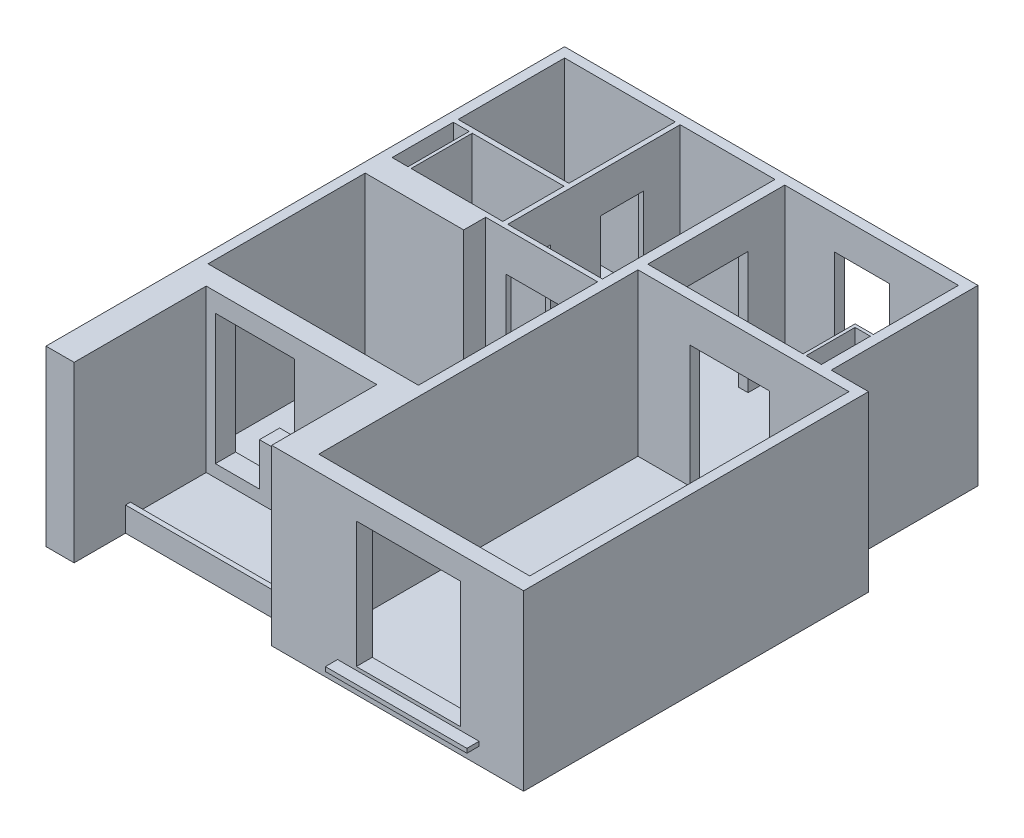
SolidWorks part; units mm, degrees
ref_plane "Спереди" through (0, 0, 0) normal (0, 0, 1) x (1, 0, 0)
ref_plane "Сверху" through (0, 0, 0) normal (0, 1, 0) x (1, 0, 0)
ref_plane "Справа" through (0, 0, 0) normal (1, 0, 0) x (0, 0, -1)
other "Configuration Table"
sketch "чертеж" plane through (0, 0, 0) normal (0, 1, 0) x (1, 0, 0)
  line L0 (-122.4645, -5934.5928) -> (200.8688, -5934.5928) construction
  line L1 (11.3792, -6202.3586) -> (334.7125, -6202.3586) construction
  line L2 (-29.7674, 42.6262) -> (294.8993, 42.6262) construction
  line L3 (-41.8231, 39.2884) -> (282.8435, 39.2884) construction
  line L4 (2418.4622, -1094.6493) -> (2743.1288, -1094.6493) construction
  line L5 (-60.4594, 42.9789) -> (264.2073, 42.9789) construction
  line L6 (-48.7728, 66.0913) -> (275.8939, 66.0913) construction
  line L7 (-42.5542, 93.9023) -> (282.1124, 93.9023) construction
  line L8 (134.2311, 87.3942) -> (458.8978, 87.3942) construction
  line L9 (-47.3906, 51.9395) -> (277.2761, 51.9395) construction
  line L10 (-66.0858, -48.647) -> (431.2475, -48.647) construction
sketch "Эскиз по чертежу" plane through (0, 0, 0) normal (0, 1, 0) x (1, 0, 0)
  line L0 (0, 0) -> (0, 8400) construction
  line L1 (0, 8400) -> (1925, 8400) construction
  line L2 (6600, 8400) -> (6600, 6000) construction
  line L4 (7200, 6000) -> (7200, 600) construction
  line L5 (7200, 600) -> (3600, 600) construction
  line L6 (3600, 600) -> (3600, 8400) construction
  line L7 (3600, 2400) -> (0, 2400) construction
  line L8 (3600, 5475) -> (0, 5475) construction
  line L32 (6600, 6000) -> (7200, 6000) construction
  line L33 (0, 870) -> (3600, 870) construction
  line L37 (0, 1050) -> (3600, 1050) construction
  line L40 (1925, 5475) -> (1925, 6550) construction
  line L42 (1925, 6550) -> (1925, 8400) construction
  line L45 (1925, 8400) -> (3600, 8400) construction
  line L46 (3600, 8400) -> (6600, 8400) construction
  line L49 (1925, 6550) -> (0, 6550) construction
  dimension "D1" = 600
  dimension "D2" = 1800
  dimension "D3" = 3600
  dimension "D4" = 1530
  dimension "D5" = 600
  dimension "D6" = 3600
  dimension "D7" = 3600
  dimension "D8" = 2400
  dimension "D9" = 2925
  dimension "D10" = 1925
  dimension "D11" = 1850
  dimension "D12" = 1350
sketch "Эскиз3" plane through (0, 0, 0) normal (0, 1, 0) x (1, 0, 0)
  line L1 (3520, 6130) -> (3680, 6130)
  line L2 (4555, 700) -> (4555, 1200) construction
  line L11 (80, 8320) -> (3520, 8320)
  line L15 (3520, 8320) -> (3520, 7720)
  line L16 (3520, 7720) -> (3680, 7720)
  line L17 (3680, 7720) -> (3680, 8320)
  line L20 (6520, 6080) -> (5830, 6080)
  line L21 (-80, 8480) -> (4495, 8480)
  line L22 (6520, 8320) -> (6520, 6080)
  line L24 (4495, 8480) -> (4495, 8320)
  line L25 (4495, 8320) -> (3680, 8320)
  line L26 (6680, 8480) -> (5395, 8480)
  line L29 (7130, 5920) -> (7130, 700)
  line L30 (4555, 700) -> (3680, 700)
  line L32 (6255, 540) -> (7290, 540)
  line L33 (7290, 540) -> (7290, 6080)
  line L34 (7290, 6080) -> (6680, 6080)
  line L35 (6680, 6080) -> (6680, 8480)
  line L39 (5395, 8480) -> (5395, 8320)
  line L40 (5395, 8320) -> (6520, 8320)
  line L41 (5830, 6080) -> (5830, 5920)
  line L42 (5830, 5920) -> (7130, 5920)
  line L45 (-80, 8480) -> (-80, 0)
  line L46 (-80, 0) -> (80, 0)
  line L47 (3680, 6080) -> (4530, 6080)
  line L52 (80, 0) -> (80, 8320)
  line L60 (3680, 700) -> (3680, 5920)
  line L68 (3520, 6130) -> (3520, 540)
  line L69 (4530, 6080) -> (4530, 5920)
  line L70 (4530, 5920) -> (3680, 5920)
  line L71 (7130, 700) -> (6255, 700)
  line L72 (6255, 540) -> (6255, 700)
  line L73 (3520, 540) -> (4555, 540)
  line L74 (4555, 540) -> (4555, 700)
  line L76 (4555, 1200) -> (3680, 1200) construction
  line L77 (6255, 700) -> (6255, 1200) construction
  line L78 (4555, 1200) -> (6255, 1200) construction
  line L79 (6255, 1200) -> (7130, 1200) construction
  line L80 (3680, 6130) -> (3680, 6080)
  line L81 (3600, 8400) -> (6600, 8400) construction
  line L83 (0, 0) -> (0, 8400) construction
  dimension "D1" = 3440
  dimension "D2" = 3450
  dimension "D3" = 5220
  dimension "D4" = 1300
  dimension "D5" = 160
  dimension "D6" = 2840
  dimension "D7" = 160
  dimension "D8" = 160
  dimension "D9" = 2240
  dimension "D10" = 160
  dimension "D11" = 80
  dimension "D12" = 160
  dimension "D13" = 160
  dimension "D14" = 80
  dimension "D15" = 900
  dimension "D16" = 160
  dimension "D17" = 1125
  dimension "D18" = 600
  dimension "D19" = 160
  dimension "D20" = 850
  dimension "D21" = 1700
  dimension "D22" = 500
  dimension "D23" = 50
  dimension "D24" = 875
extrude "несущие стены" add sketch "Эскиз3" along normal blind 2640 separate body
sketch "Эскиз8" plane through (0, 0, 0) normal (0, 1, 0) x (1, 0, 0)
  line L0 (80, 8320) -> (3520, 8320) construction
  line L1 (80, 5500) -> (1690, 5500)
  line L2 (80, 5500) -> (80, 5060)
  line L3 (80, 5060) -> (1690, 5060)
  line L4 (1690, 5500) -> (1690, 5060)
  line L10 (80, 0) -> (80, 8320) construction
  dimension "D1" = 440
  dimension "D2" = 2820
  dimension "D5" = 1610
extrude "вытяжка кухня" add sketch "Эскиз8" along normal up to surface (2640 mm away) up to face at (6442.8571, 2640, -5160)
sketch "Эскиз5" plane through (0, 0, 0) normal (0, 1, 0) x (1, 0, 0)
  line L0 (80, 6580) -> (1890, 6580)
  line L1 (1970, 6200) -> (1970, 5500) construction
  line L2 (1890, 6580) -> (1890, 7020)
  line L3 (1890, 7020) -> (1970, 7020)
  line L4 (1970, 7020) -> (1970, 6200)
  line L5 (1970, 6200) -> (1890, 6200)
  line L6 (1890, 6200) -> (1890, 6500)
  line L7 (1890, 6500) -> (80, 6500)
  line L9 (80, 6500) -> (80, 6580)
  line L10 (1690, 5420) -> (2020, 5420)
  line L12 (2020, 5420) -> (2020, 5500)
  line L17 (2020, 5500) -> (1690, 5500)
  line L18 (1690, 5500) -> (1690, 5420)
  line L19 (3520, 5420) -> (2920, 5420)
  line L20 (3520, 6130) -> (3520, 540) construction
  line L21 (2920, 5420) -> (2920, 5500)
  line L22 (2920, 5500) -> (3520, 5500)
  line L23 (80, 0) -> (80, 5060) construction
  line L24 (3520, 5500) -> (3520, 5420)
  line L25 (1890, 8320) -> (1890, 7720)
  line L27 (1890, 7720) -> (1970, 7720)
  line L28 (1970, 7720) -> (1970, 8320)
  line L30 (1970, 8320) -> (1890, 8320)
  line L31 (80, 8320) -> (3520, 8320) construction
  line L32 (3520, 8320) -> (3520, 7720) construction
  dimension "D1" = 600
  dimension "D2" = 1810
  dimension "D3" = 1550
  dimension "D4" = 1740
  dimension "D5" = 80
  dimension "D6" = 700
  dimension "D7" = 700
  dimension "D8" = 1000
  dimension "D9" = 900
  dimension "D10" = 50
  dimension "D11" = 80
  dimension "D12" = 80
extrude "перегородки санузла" add sketch "Эскиз5" along normal up to surface (2640 mm away) up to face at (1923.5714, 2640, -6200)
sketch "Эскиз7" plane through (0, 0, 0) normal (0, 1, 0) x (1, 0, 0)
  line L0 (80, 0) -> (80, 5060) construction
  line L1 (530, 2490) -> (80, 2490)
  line L2 (380, 2160) -> (380, 0)
  line L3 (3170, 2160) -> (3170, 440)
  line L4 (3170, 440) -> (4555, 440)
  line L5 (380, 0) -> (80, 0)
  line L6 (80, 2490) -> (80, 0)
  line L7 (2920, 5420) -> (3520, 5420) construction
  line L8 (3170, 2160) -> (1820, 2160)
  line L9 (3520, 540) -> (4555, 540) construction
  line L10 (1820, 2490) -> (3520, 2490)
  line L14 (80, 5060) -> (1690, 5060) construction
  line L19 (4555, 540) -> (4555, 440)
  line L20 (6255, 540) -> (7290, 540)
  line L21 (6255, 540) -> (6255, 440)
  line L22 (6255, 440) -> (7290, 440)
  line L23 (7290, 540) -> (7290, 440)
  line L24 (1820, 2160) -> (1820, 2490)
  line L25 (3520, 2490) -> (3520, 540)
  line L26 (3520, 540) -> (4555, 540)
  line L27 (3520, 5420) -> (3520, 540) construction
  line L28 (6255, 540) -> (7290, 540) construction
  line L29 (380, 2160) -> (530, 2160)
  line L30 (530, 2160) -> (530, 2490)
  line L31 (4555, 540) -> (4555, 700) construction
  line L32 (6255, 700) -> (6255, 540) construction
  dimension "D1" = 2790
  dimension "D2" = 100
  dimension "D3" = 330
  dimension "D4" = 1290
  dimension "D5" = 150
  dimension "D6" = 450
  dimension "D7" = 2930
  dimension "D8" = 2570
extrude "лоджия" add sketch "Эскиз7" along normal up to surface (2640 mm away) up to face at (1798.2143, 2640, -6511.4286)
sketch "Эскиз9" plane through (0, 0, 0) normal (0, 1, 0) x (1, 0, 0)
  line L0 (340, 6500) -> (390, 6500)
  line L1 (6520, 6930) -> (6220, 6930)
  line L4 (6220, 6930) -> (6220, 6080)
  line L5 (80, 6500) -> (1890, 6500) construction
  line L6 (6520, 6080) -> (5830, 6080) construction
  line L7 (6270, 6880) -> (6520, 6880)
  line L8 (6270, 6880) -> (6270, 6080)
  line L11 (6520, 8320) -> (6520, 6080) construction
  line L13 (390, 5500) -> (340, 5500)
  line L14 (390, 6500) -> (390, 5500)
  line L15 (2020, 5500) -> (80, 5500) construction
  line L19 (340, 6500) -> (340, 5500)
  line L22 (1890, 6500) -> (1890, 6200) construction
  line L24 (6520, 6930) -> (6520, 6880)
  line L25 (6220, 6080) -> (6270, 6080)
  point P13 (6370, 6930)
  dimension "D1" = 850
  dimension "D2" = 50
  dimension "D4" = 300
  dimension "D8" = 50
  dimension "D11" = 1500
extrude "зсс" add sketch "Эскиз9" along normal up to surface (2640 mm away) up to face at (6442.8571, 2640, -5145.7143)
sketch "Эскиз11" plane through (0, 0, 0) normal (0, 1, 0) x (1, 0, 0)
  line L1 (1820, 2490) -> (1250, 2490)
  line L2 (1820, 2490) -> (1820, 2160)
  line L3 (1820, 2160) -> (1250, 2160)
  line L4 (1250, 2490) -> (1250, 2160)
  line L5 (530, 2160) -> (530, 2490) construction
  dimension "D1" = 720
extrude "лоджияперегородка" add sketch "Эскиз11" along normal blind 900
sketch "Эскиз4" plane through (0, 0, 0) normal (0, 1, 0) x (1, 0, 0)
  line L8 (-80, 8480) -> (6680, 8480)
  line L9 (6680, 8480) -> (6680, 6080)
  line L10 (6680, 6080) -> (7290, 6080)
  line L11 (7290, 6080) -> (7290, 440)
  line L13 (3170, 440) -> (3170, 840)
  line L14 (3170, 840) -> (380, 840)
  line L17 (-80, 0) -> (-80, 8480)
  line L18 (6680, 6080) -> (6680, 8480) construction
  line L19 (6680, 8480) -> (5395, 8480) construction
  line L20 (380, 920) -> (3170, 920) construction
  line L21 (380, 0) -> (380, 2160) construction
  line L22 (3170, 2160) -> (3170, 440) construction
  line L24 (380, 840) -> (380, 0)
  line L25 (380, 0) -> (-80, 0)
  line L26 (3170, 440) -> (7290, 440)
  line L27 (1820, 2160) -> (3170, 2160) construction
  line L28 (380, 0) -> (380, 2160) construction
  line L29 (-80, 0) -> (380, 0) construction
  dimension "D1" = 80
  dimension "D2" = 1240
extrude "пол" add sketch "Эскиз4" against normal blind 200
sketch "Эскиз49" plane through (0, 0, 0) normal (0, 1, 0) x (1, 0, 0)
  line L0 (380, 0) -> (380, 2160) construction
  line L1 (3170, 840) -> (380, 840)
  line L2 (3170, 840) -> (3170, 920)
  line L3 (3170, 920) -> (380, 920)
  line L4 (380, 840) -> (380, 920)
  dimension "D1" = 80
extrude "лоджиябордюрподокно" add sketch "Эскиз49" along normal blind 200
sketch "Эскиз50" plane through (0, 0, -440) normal (0, 0, 1) x (1, 0, 0)
  line L0 (4555, 0) -> (6255, 0) construction
  line L1 (4247.5, 145) -> (6562.5, 145)
  line L2 (4247.5, 145) -> (4247.5, 75)
  line L3 (4247.5, 75) -> (6562.5, 75)
  line L4 (6562.5, 145) -> (6562.5, 75)
  line L5 (5405, 0) -> (5405, 75) construction
  point P4 (5405, 75)
  point P5 (5405, 0)
  dimension "D1" = 70
  dimension "D2" = 2315
  dimension "D3" = 75
sketch "Эскиз54" plane through (0, 0, 0) normal (0, 1, 0) x (1, 0, 0)
  line L1 (530, 2490) -> (1250, 2490)
  line L2 (530, 2490) -> (530, 2160)
  line L3 (530, 2160) -> (1250, 2160)
  line L4 (1250, 2490) -> (1250, 2160)
extrude "лоджиябордюрподдверь" add sketch "Эскиз54" along normal blind 200
sketch "Эскиз51" plane through (0, 0, 0) normal (0, 1, 0) x (1, 0, 0)
  line L0 (4555, 440) -> (4555, 700) construction
  line L1 (6255, 440) -> (4555, 440)
  line L2 (6255, 440) -> (6255, 700)
  line L3 (6255, 700) -> (4555, 700)
  line L4 (4555, 440) -> (4555, 700)
extrude "залбордярподконо" add sketch "Эскиз51" along normal blind 200
extrude "подоконникнаружний" add sketch "Эскиз50" along normal blind 200
sketch "Эскиз53" plane through (0, 2640, 0) normal (0, 1, 0) x (1, 0, 0)
  line L1 (1820, 2490) -> (530, 2490)
  line L2 (1820, 2490) -> (1820, 2160)
  line L3 (1820, 2160) -> (530, 2160)
  line L4 (530, 2490) -> (530, 2160)
extrude "лоджияверх" add sketch "Эскиз53" against normal blind 310
sketch "Эскиз52" plane through (0, 2640, 0) normal (0, 1, 0) x (1, 0, 0)
  line L1 (4555, 440) -> (6255, 440)
  line L2 (4555, 440) -> (4555, 700)
  line L3 (4555, 700) -> (6255, 700)
  line L4 (6255, 440) -> (6255, 700)
extrude "залокноверх" add sketch "Эскиз52" against normal blind 380
sketch "Эскиз55" plane through (0, 2640, 0) normal (0, 1, 0) x (1, 0, 0)
  line L1 (4495, 8480) -> (5395, 8480)
  line L2 (4495, 8480) -> (4495, 8320)
  line L3 (4495, 8320) -> (5395, 8320)
  line L4 (5395, 8480) -> (5395, 8320)
extrude "входнаядверьверх" add sketch "Эскиз55" against normal blind 540
sketch "Эскиз65" plane through (0, 2640, 0) normal (0, 1, 0) x (1, 0, 0)
  line L0 (2020, 5500) -> (390, 5500) construction
  line L1 (1890, 6200) -> (1970, 6200)
  line L2 (1890, 6200) -> (1890, 5500)
  line L3 (1890, 5500) -> (1970, 5500)
  line L4 (1970, 6200) -> (1970, 5500)
  line L6 (1890, 7720) -> (1970, 7720)
  line L7 (1890, 7720) -> (1890, 7020)
  line L8 (1890, 7020) -> (1970, 7020)
  line L9 (1970, 7720) -> (1970, 7020)
  line L10 (3520, 7720) -> (3680, 7720)
  line L11 (3520, 7720) -> (3520, 6130)
  line L12 (3520, 6130) -> (3680, 6130)
  line L13 (3680, 7720) -> (3680, 6130)
  line L14 (2020, 5500) -> (2920, 5500)
  line L15 (2020, 5500) -> (2020, 5420)
  line L16 (2020, 5420) -> (2920, 5420)
  line L17 (2920, 5500) -> (2920, 5420)
  line L18 (4530, 6080) -> (5830, 6080)
  line L19 (4530, 6080) -> (4530, 5920)
  line L20 (4530, 5920) -> (5830, 5920)
  line L21 (5830, 6080) -> (5830, 5920)
extrude "остальные" add sketch "Эскиз65" against normal offset from surface (640 mm away) 2000 up to face at (3271.25, 0, -6277.0833)
sketch "Эскиз что надо" [suppressed] plane through (0, 0, 0) normal (0, 1, 0) x (1, 0, 0)
  line L0 (5525, 8300) -> (5525, 6100) construction
  line L5 (2000, 6240) -> (2000, 7000) construction
  line L6 (1850, 7000) -> (2000, 7000)
  line L7 (1850, 7000) -> (1850, 6620)
  line L8 (1850, 6620) -> (2000, 6620)
  line L9 (2000, 7000) -> (2000, 6620)
  line L10 (1850, 6490) -> (1850, 6240) construction
  line L11 (1850, 7700) -> (2000, 7700)
  line L12 (1850, 7700) -> (1850, 7320)
  line L13 (1850, 7320) -> (2000, 7320)
  line L14 (2000, 7700) -> (2000, 7320)
  line L15 (1850, 5540) -> (2000, 5540)
  line L16 (1850, 5540) -> (1850, 5790)
  line L17 (1850, 5790) -> (2000, 5790)
  line L18 (2000, 5540) -> (2000, 5790)
  line L19 (1850, 6490) -> (2000, 6490)
  line L20 (1850, 6490) -> (1850, 6240)
  line L21 (1850, 6240) -> (2000, 6240)
  line L22 (2000, 6490) -> (2000, 6240)
  line L23 (1850, 7000) -> (1850, 6620) construction
  line L28 (3500, 7700) -> (3700, 7700) construction
  line L29 (3500, 7700) -> (3500, 7420) construction
  line L30 (3500, 7420) -> (3700, 7420) construction
  line L31 (3700, 7700) -> (3700, 7420) construction
  line L32 (4550, 5900) -> (4550, 6100) construction
  line L35 (5850, 5900) -> (5450, 5900)
  line L36 (5850, 5900) -> (5850, 6100)
  line L37 (5850, 6100) -> (5450, 6100)
  line L38 (5450, 5900) -> (5450, 6100)
  line L39 (5375, 8300) -> (6500, 8300) construction
  line L40 (2000, 7420) -> (3500, 7420) construction
  line L41 (5375, 8500) -> (5375, 8300) construction
  line L42 (2380, 5540) -> (400, 5540) construction
  line L43 (1284, 2540) -> (2160, 2540)
  line L44 (1284, 2540) -> (1284, 2190)
  line L46 (1284, 2190) -> (2160, 2190)
  line L47 (2000, 7320) -> (2000, 6620) construction
  line L48 (2160, 2540) -> (2160, 2190)
  point P32 (1925, 6490)
  dimension "D8" = 900
  dimension "D1" = 700
  dimension "D2" = 700
  dimension "D3" = 150
  dimension "D5" = 100
sketch "Эскиз13" [suppressed] plane through (0, 0, 0) normal (0, 1, 0) x (1, 0, 0)
  line L1 (1850, 6490) -> (2000, 6490)
  line L2 (1850, 6490) -> (1850, 6240)
  line L3 (1850, 6240) -> (2000, 6240)
  line L4 (2000, 6490) -> (2000, 6240)
  line L5 (1850, 7000) -> (2000, 7000)
  line L6 (1850, 7000) -> (1850, 6620)
  line L7 (1850, 6620) -> (2000, 6620)
  line L8 (2000, 7000) -> (2000, 6620)
  line L9 (1284, 2540) -> (2160, 2540) construction
  line L10 (1284, 2540) -> (1284, 2190) construction
  line L11 (1284, 2190) -> (2160, 2190) construction
  line L12 (2160, 2540) -> (2160, 2190) construction
extrude "санузел вырез" [suppressed] cut sketch "Эскиз13" along normal through all
sketch "Эскиз14" [suppressed] plane through (0, 0, 0) normal (0, 1, 0) x (1, 0, 0)
  line L1 (5850, 6100) -> (5450, 6100)
  line L2 (5850, 6100) -> (5850, 5900)
  line L3 (5850, 5900) -> (5450, 5900)
  line L4 (5450, 6100) -> (5450, 5900)
  line L5 (1850, 5540) -> (2000, 5540)
  line L6 (1850, 5540) -> (1850, 5790)
  line L7 (1850, 5790) -> (2000, 5790)
  line L8 (2000, 5540) -> (2000, 5790)
  line L9 (1850, 7700) -> (2000, 7700)
  line L10 (1850, 7700) -> (1850, 7320)
  line L11 (1850, 7320) -> (2000, 7320)
  line L12 (2000, 7700) -> (2000, 7320)
extrude "наращивание стен" [suppressed] add sketch "Эскиз14" along normal through all separate body
sketch "Эскиз15" [suppressed] plane through (0, 0, 0) normal (0, 1, 0) x (1, 0, 0)
  line L12 (3700, 7700) -> (3500, 7700) construction
  line L29 (3700, 7420) -> (3700, 7700)
  line L30 (3700, 7700) -> (3500, 7700)
  line L32 (3500, 7700) -> (3500, 7420)
  line L36 (3500, 7420) -> (3700, 7420)
  line L39 (3500, 7700) -> (3500, 7420) construction
  line L40 (3700, 7700) -> (3700, 7420) construction
  line L46 (3500, 7700) -> (3700, 7700) construction
  line L47 (2000, 7420) -> (2800, 7420) construction
  line L48 (2000, 7420) -> (2000, 7500) construction
  line L49 (2000, 7500) -> (2800, 7500) construction
  line L50 (2800, 7420) -> (2800, 7500) construction
  dimension "D1" = 80
  dimension "D2" = 700
extrude "наращивание стен 2" [suppressed] add sketch "Эскиз15" along normal through all separate body
sketch "Эскиз37" [suppressed] plane through (0, 0, 0) normal (0, 1, 0) x (1, 0, 0)
  line L0 (3700, 700) -> (7100, 700)
  line L1 (7100, 700) -> (7100, 5900)
  line L2 (7100, 5900) -> (5850, 5900)
  line L3 (5850, 5900) -> (5850, 6100)
  line L7 (5850, 6100) -> (4550, 6100)
  line L8 (4550, 6100) -> (4550, 5900)
  line L9 (4550, 5900) -> (3700, 5900)
  line L10 (3700, 5900) -> (3700, 700)
extrude "зал" [suppressed] add sketch "Эскиз37" along normal blind 50 separate body
sketch "Эскиз38" [suppressed] plane through (0, 0, 0) normal (0, 1, 0) x (1, 0, 0)
  line L0 (460, 950) -> (3160, 950)
  line L1 (3160, 950) -> (3160, 2190)
  line L2 (3160, 2190) -> (2160, 2190)
  line L3 (2160, 2190) -> (2160, 2540)
  line L4 (2160, 2540) -> (3500, 2540)
  line L5 (3500, 5410) -> (3500, 2540) construction
  line L6 (3500, 2540) -> (3500, 5410)
  line L7 (3500, 5410) -> (3280, 5410)
  line L8 (3280, 5410) -> (3280, 5540)
  line L9 (3280, 5540) -> (2380, 5540)
  line L10 (2380, 5540) -> (2380, 5410)
  line L11 (2380, 5410) -> (1710, 5410)
  line L12 (1710, 5410) -> (1710, 5060)
  line L13 (1710, 5060) -> (100, 5060)
  line L14 (100, 5060) -> (100, 2540)
  line L15 (100, 2540) -> (560, 2540)
  line L16 (560, 2540) -> (560, 2190)
  line L17 (560, 2190) -> (460, 2190)
  line L18 (460, 2190) -> (460, 950)
  line L19 (460, 0) -> (460, 2190) construction
  line L20 (460, 900) -> (3160, 900) construction
  line L21 (3500, 2540) -> (2160, 2540) construction
  line L22 (3500, 2540) -> (1284, 2540) construction
  dimension "D1" = 50
extrude "кухня лоджия" [suppressed] add sketch "Эскиз38" along normal blind 50 separate body
sketch "Эскиз40" [suppressed] plane through (0, 0, 0) normal (0, 1, 0) x (1, 0, 0)
  line L0 (6200, 6100) -> (6200, 6950)
  line L1 (6200, 6950) -> (6500, 6950)
  line L2 (6500, 6950) -> (6500, 8300)
  line L3 (6500, 8300) -> (3700, 8300)
  line L4 (3700, 8300) -> (3700, 7420)
  line L5 (3700, 7420) -> (3500, 7420)
  line L6 (3500, 7420) -> (3500, 8300)
  line L7 (3500, 8300) -> (2000, 8300)
  line L8 (2000, 8300) -> (2000, 5540)
  line L9 (2000, 5540) -> (3500, 5540)
  line L10 (3500, 5540) -> (3500, 6100)
  line L11 (3500, 6100) -> (6200, 6100)
extrude "прихожия" [suppressed] add sketch "Эскиз40" along normal blind 50 separate body
sketch "Эскиз42" [suppressed] plane through (0, 0, 0) normal (0, 1, 0) x (1, 0, 0)
  line L0 (100, 8300) -> (100, 6620)
  line L1 (100, 6620) -> (2000, 6620)
  line L4 (2000, 6620) -> (2000, 7320)
  line L5 (2000, 7320) -> (1850, 7320)
  line L6 (1850, 7320) -> (1850, 8300)
  line L7 (1850, 8300) -> (100, 8300)
  line L8 (2000, 8300) -> (2000, 5540) construction
  line L9 (2000, 6620) -> (100, 6620) construction
  line L10 (2000, 8300) -> (2000, 5540) construction
extrude "ванная" [suppressed] add sketch "Эскиз42" along normal blind 50 separate body
sketch "Эскиз45" [suppressed] plane through (0, 50, 0) normal (0, 1, 0) x (1, 0, 0)
  line L0 (400, 6490) -> (2000, 6490) construction
  line L1 (850, 6490) -> (930, 6490)
  line L2 (850, 6490) -> (850, 5540)
  line L3 (850, 5540) -> (930, 5540)
  line L4 (930, 6490) -> (930, 5540)
  line L5 (2380, 5540) -> (400, 5540) construction
  line L7 (1850, 5790) -> (1850, 5540) construction
  dimension "D1" = 80
  dimension "D2" = 920
extrude "Бобышка-Вытянуть33" [suppressed] add sketch "Эскиз45" along normal blind 1200 separate body
sketch "Эскиз46" [suppressed] plane through (930, 0, 0) normal (1, 0, 0) x (0, 0, -1)
  line L0 (5540, 50) -> (6490, 50) construction
  line L1 (5835, 440) -> (6195, 440)
  line L2 (5835, 440) -> (5835, 80)
  line L3 (5835, 80) -> (6195, 80)
  line L4 (6195, 440) -> (6195, 80)
  line L6 (6015, 50) -> (6015, 440) construction
  line L7 (6490, 1250) -> (6490, 50) construction
  line L8 (6015, 440) -> (6015, 950) construction
  line L9 (5940, 1040) -> (6090, 1040)
  line L10 (5940, 1040) -> (5940, 950)
  line L11 (5940, 950) -> (6090, 950)
  line L12 (6090, 1040) -> (6090, 950)
  line L14 (6280, 550) -> (6480, 550)
  line L15 (6280, 550) -> (6280, 50)
  line L16 (6280, 50) -> (6480, 50)
  line L17 (6480, 550) -> (6480, 50)
  point P4 (6015, 50)
  dimension "D1" = 360
  dimension "D2" = 390
  dimension "D3" = 150
  dimension "D4" = 90
  dimension "D5" = 900
  dimension "D6" = 30
  dimension "D7" = 200
  dimension "D8" = 500
  dimension "D9" = 10
extrude "Вырез-Вытянуть2" [suppressed] cut sketch "Эскиз46" against normal up to surface (80 mm away)
sketch "Эскиз43" [suppressed] plane through (0, 0, 0) normal (0, 1, 0) x (1, 0, 0)
  line L0 (930, 6490) -> (930, 5540)
  line L1 (930, 5540) -> (1850, 5540)
  line L2 (2380, 5540) -> (400, 5540) construction
  line L3 (1850, 5540) -> (1850, 5790)
  line L4 (1850, 5790) -> (2000, 5790)
  line L5 (2000, 5790) -> (2000, 6490)
  line L8 (2000, 6490) -> (930, 6490)
extrude "толчок" [suppressed] add sketch "Эскиз43" along normal blind 50 separate body
sketch "Эскиз47" [suppressed] plane through (0, 0, 0) normal (0, 1, 0) x (1, 0, 0)
  line L0 (3500, 5410) -> (3500, 2540) construction
  line L1 (1710, 6490) -> (3500, 6490) construction
  line L2 (1710, 6490) -> (1710, 4290) construction
  line L3 (1710, 4290) -> (3500, 4290) construction
  line L4 (3500, 6490) -> (3500, 4290) construction
  line L5 (1560, 5410) -> (1560, 6620) construction
  line L6 (400, 6490) -> (1850, 6490) construction
  line L7 (1710, 5060) -> (1710, 5410) construction
  line L8 (100, 5410) -> (1660, 5410) construction
  line L9 (2000, 6240) -> (2000, 7000) construction
  line L10 (1850, 6620) -> (100, 6620) construction
  line L11 (1850, 8300) -> (2000, 8300)
  line L12 (1850, 8300) -> (1850, 6620)
  line L13 (1560, 6620) -> (1710, 6620) construction
  line L14 (1710, 6620) -> (1710, 6490) construction
  line L15 (1850, 6620) -> (2000, 6620)
  line L16 (2000, 8300) -> (2000, 6620)
  line L17 (3500, 5410) -> (3500, 2540) construction
  line L18 (3500, 3840) -> (3700, 3840)
  line L19 (3500, 3840) -> (3500, 3140)
  line L20 (3500, 3140) -> (3700, 3140)
  line L21 (3700, 3840) -> (3700, 3140)
  line L22 (3700, 700) -> (3700, 5900) construction
  line L24 (3500, 2540) -> (100, 2540) construction
  line L25 (2000, 6240) -> (2000, 7000) construction
  line L26 (400, 6490) -> (1560, 6490)
  line L27 (400, 6490) -> (400, 6620)
  line L28 (400, 6620) -> (1560, 6620)
  line L29 (1560, 6490) -> (1560, 6620)
  line L30 (3500, 5540) -> (1710, 5540)
  line L31 (3500, 5540) -> (3500, 5410)
  line L32 (3500, 5410) -> (1710, 5410)
  line L33 (1710, 5540) -> (1710, 5410)
  line L34 (1850, 6490) -> (2000, 6490)
  line L35 (1850, 6490) -> (1850, 6240)
  line L36 (1850, 6240) -> (2000, 6240)
  line L37 (2000, 6490) -> (2000, 6240)
  dimension "D1" = 700
  dimension "D2" = 2200
  dimension "D3" = 600
extrude "Вырез-Вытянуть3" [suppressed] cut sketch "Эскиз47" along normal through all
sketch "Эскиз48" [suppressed] plane through (0, 0, 0) normal (0, 1, 0) x (1, 0, 0)
  line L0 (5850, 5900) -> (7100, 5900) construction
  line L1 (1560, 6490) -> (1710, 6490)
  line L2 (1560, 6490) -> (1560, 5540)
  line L3 (1560, 5540) -> (1710, 5540)
  line L4 (1710, 6490) -> (1710, 5540)
  line L5 (5850, 6100) -> (5375, 6100)
  line L6 (5850, 6100) -> (5850, 5900)
  line L7 (5850, 5900) -> (5375, 5900)
  line L8 (5375, 6100) -> (5375, 5900)
  line L11 (3700, 6620) -> (3700, 6100)
  line L12 (2000, 6490) -> (3500, 6490)
  line L13 (3500, 6490) -> (3500, 6100)
  line L14 (3500, 6100) -> (3700, 6100)
  line L15 (3500, 6100) -> (3500, 3840) construction
  line L16 (4550, 6100) -> (3500, 6100) construction
  line L17 (3700, 3840) -> (3700, 5900) construction
  line L18 (2000, 6490) -> (2000, 6620)
  line L19 (3700, 7700) -> (3500, 7700)
  line L20 (3500, 7700) -> (3500, 7320)
  line L21 (3500, 7320) -> (3700, 7320)
  line L22 (3700, 7320) -> (3700, 7700)
  line L23 (3700, 6620) -> (2000, 6620)
  line L24 (3700, 3840) -> (3500, 3840) construction
  line L25 (3700, 4090) -> (5300, 4090) construction
  line L26 (3700, 4090) -> (3700, 3990) construction
  line L27 (3700, 3990) -> (5300, 3990) construction
  line L28 (5300, 4090) -> (5300, 3990) construction
  line L29 (7100, 5900) -> (7100, 700) construction
  line L30 (5375, 8300) -> (5375, 6100) construction
  line L31 (4550, 5900) -> (4550, 6100) construction
  dimension "D1" = 825
  dimension "D2" = 700
  dimension "D3" = 100
  dimension "D4" = 150
  dimension "D5" = 1800
extrude "Бобышка-Вытянуть34" [suppressed] add sketch "Эскиз48" along normal through all
sketch "Эскиз60" [suppressed] plane through (0, 0, 0) normal (0, 1, 0) x (1, 0, 0)
  line L0 (1560, 5540) -> (400, 5540) construction
  line L1 (400, 6620) -> (560, 6620)
  line L2 (400, 6620) -> (400, 5540)
  line L3 (400, 5540) -> (560, 5540)
  line L4 (560, 6620) -> (560, 5540)
  dimension "D1" = 160
extrude "утолщениедлядуша" [suppressed] add sketch "Эскиз60" along normal up to surface (2640 mm away) up to face at (5405, 2640, -3310)
sketch "Эскиз61" [suppressed] plane through (0, 0, 0) normal (0, 1, 0) x (1, 0, 0)
  line L0 (1850, 6620) -> (100, 6620) construction
  line L1 (1850, 8300) -> (2000, 8300)
  line L2 (1850, 8300) -> (1850, 6620)
  line L3 (1850, 6240) -> (2000, 6240)
  line L4 (2000, 8300) -> (2000, 6240)
  line L5 (3500, 5540) -> (1710, 5540)
  line L6 (3500, 5540) -> (3500, 5410)
  line L7 (3500, 5410) -> (1710, 5410)
  line L8 (1710, 5540) -> (1710, 5410)
  line L9 (400, 6490) -> (1850, 6490)
  line L10 (400, 6490) -> (400, 6620)
  line L11 (400, 6620) -> (1850, 6620)
  line L13 (1850, 6490) -> (1850, 6240)
extrude "Вырез-Вытянуть4" [suppressed] cut sketch "Эскиз61" along normal up to surface (2640 mm away) up to face at (5405, 2640, -3310)
sketch "Эскиз62" [suppressed] plane through (0, 0, 0) normal (0, 1, 0) x (1, 0, 0)
  line L0 (7100, 5900) -> (7100, 700) construction
  line L1 (5100, 2900) -> (7100, 2900)
  line L2 (5100, 2900) -> (5100, 1400)
  line L3 (5100, 1400) -> (7100, 1400)
  line L4 (7100, 2900) -> (7100, 1400)
  line L5 (5850, 5900) -> (7100, 5900) construction
  line L9 (3700, 5900) -> (4550, 5900)
  line L11 (4700, 3600) -> (4700, 3750)
  line L12 (3700, 3750) -> (3900, 3750)
  line L13 (3700, 700) -> (3700, 5900) construction
  line L14 (7100, 1400) -> (7100, 700) construction
  line L15 (3900, 3750) -> (3900, 3600)
  line L16 (3900, 3600) -> (3700, 3600)
  line L17 (3700, 700) -> (3700, 5900) construction
  line L18 (3700, 3600) -> (3700, 3750)
  line L19 (4700, 3750) -> (4900, 3750)
  line L20 (4900, 3750) -> (4900, 4600)
  line L22 (7100, 4600) -> (7100, 4450)
  line L23 (7100, 5900) -> (7100, 700) construction
  line L24 (7100, 4450) -> (5050, 4450)
  line L25 (5050, 4450) -> (5050, 3600)
  line L26 (4700, 3600) -> (5050, 3600)
  line L27 (5050, 3600) -> (7100, 3600) construction
  line L28 (4900, 3750) -> (5050, 3750) construction
  line L29 (7100, 3600) -> (7100, 2900) construction
  line L30 (3700, 5900) -> (3700, 6100)
  line L31 (3900, 3600) -> (4700, 3600) construction
  line L32 (7100, 4600) -> (4900, 4600)
  line L36 (7100, 5900) -> (7100, 4600) construction
  line L37 (5850, 5900) -> (7100, 5900) construction
  line L38 (3700, 3750) -> (3700, 4550)
  line L39 (3700, 4550) -> (3500, 4550)
  line L40 (3500, 6100) -> (3500, 2540) construction
  line L41 (3500, 4550) -> (3500, 3750)
  line L42 (3500, 6100) -> (3500, 2540) construction
  line L43 (3500, 3750) -> (3700, 3750)
  line L44 (3700, 6100) -> (4550, 6100)
  line L45 (4550, 5900) -> (4550, 6100)
  line L46 (7100, 4650) -> (6300, 4650)
  line L47 (7100, 4650) -> (7100, 5900)
  line L48 (7100, 5900) -> (6300, 5900)
  line L49 (6300, 4650) -> (6300, 5900)
  line L55 (3700, 7150) -> (1710, 7150)
  line L57 (3700, 7700) -> (3700, 7150)
  line L58 (1710, 5540) -> (1560, 5540)
  line L60 (1560, 7300) -> (3500, 7300)
  line L61 (3500, 7300) -> (3500, 7700)
  line L62 (3500, 7300) -> (3500, 7150) construction
  line L63 (3500, 7700) -> (3700, 7700)
  line L64 (100, 8300) -> (3500, 8300) construction
  line L69 (1710, 7150) -> (1710, 7000)
  line L70 (1710, 7000) -> (1560, 7000)
  line L71 (1560, 7000) -> (1560, 7300)
  line L72 (1710, 5540) -> (1710, 6200)
  line L73 (1710, 6200) -> (1560, 6200)
  line L74 (1560, 6200) -> (1560, 5540)
  line L75 (3500, 5050) -> (2510, 5050)
  line L76 (3500, 6100) -> (3200, 6100)
  line L77 (3500, 6100) -> (3500, 5500)
  line L78 (3500, 5500) -> (3200, 5500)
  line L79 (3200, 6100) -> (3200, 5500)
  line L80 (2510, 5050) -> (2510, 6100)
  line L81 (2510, 6100) -> (3190, 6100)
  line L82 (3190, 6100) -> (3190, 5490)
  line L83 (3190, 5490) -> (3500, 5490)
  line L84 (3500, 5490) -> (3500, 5050)
  line L85 (3190, 6100) -> (3200, 6100) construction
  line L86 (3500, 5490) -> (3500, 5500) construction
  line L88 (100, 5060) -> (700, 5060)
  line L89 (100, 5060) -> (100, 3860)
  line L90 (100, 3860) -> (700, 3860)
  line L91 (700, 5060) -> (700, 3860)
  point P72 (1635, 6200)
  dimension "D12" = 300
  dimension "D1" = 2000
  dimension "D2" = 1500
  dimension "D3" = 700
  dimension "D4" = 800
  dimension "D5" = 150
  dimension "D6" = 200
  dimension "D7" = 1300
  dimension "D8" = 850
  dimension "D9" = 700
  dimension "D10" = 200
  dimension "D11" = 800
  dimension "D13" = 1000
  dimension "D14" = 150
  dimension "D15" = 800
  dimension "D16" = 50
  dimension "D17" = 800
  dimension "D18" = 150
  dimension "D19" = 600
  dimension "D20" = 500
  dimension "D21" = 10
  dimension "D22" = 800
  dimension "D23" = 600
  dimension "D24" = 1200
sketch "Эскиз63" [suppressed] plane through (0, 0, 0) normal (0, 1, 0) x (1, 0, 0)
  line L1 (3700, 5900) -> (4550, 5900)
  line L2 (3700, 5900) -> (3700, 6100)
  line L3 (3700, 6100) -> (4550, 6100)
  line L4 (4550, 5900) -> (4550, 6100)
  line L5 (3700, 3750) -> (3500, 3750)
  line L6 (3700, 3750) -> (3700, 4550)
  line L7 (3700, 4550) -> (3500, 4550)
  line L8 (3500, 3750) -> (3500, 4550)
extrude "Вырез-Вытянуть6" [suppressed] cut sketch "Эскиз63" along normal through all
sketch "Эскиз64" [suppressed] plane through (0, 0, 0) normal (0, 1, 0) x (1, 0, 0)
  line L0 (4700, 3600) -> (5050, 3600)
  line L1 (3700, 3600) -> (3900, 3600)
  line L2 (3700, 3600) -> (3700, 3750)
  line L3 (3700, 3750) -> (3900, 3750)
  line L4 (3900, 3600) -> (3900, 3750)
  line L5 (5050, 3600) -> (5050, 4450)
  line L6 (5050, 4450) -> (7100, 4450)
  line L7 (7100, 4450) -> (7100, 4600)
  line L8 (7100, 4600) -> (4900, 4600)
  line L9 (4900, 4600) -> (4900, 3750)
  line L10 (4900, 3750) -> (4700, 3750)
  line L11 (4700, 3750) -> (4700, 3600)
extrude "Бобышка-Вытянуть35" [suppressed] add sketch "Эскиз64" along normal through all
